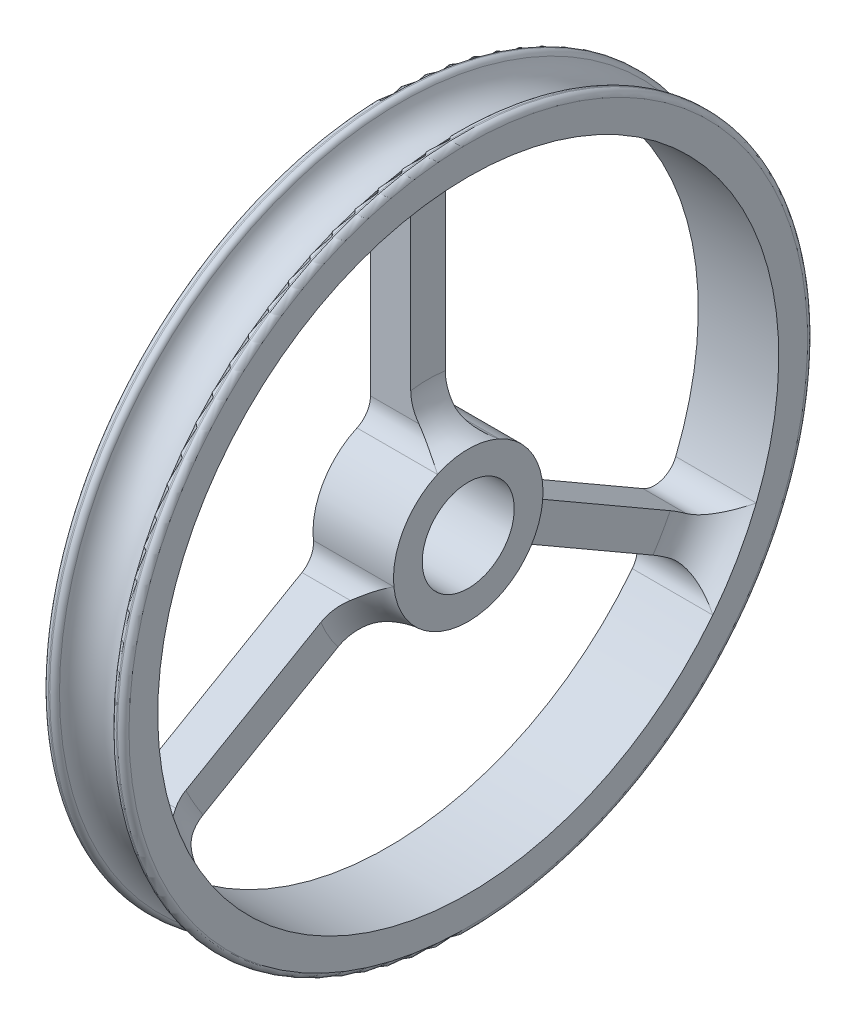
SolidWorks part; units mm, degrees
ref_plane "Front Plane" through (0, 0, 0) normal (0, 0, 1) x (1, 0, 0)
ref_plane "Top Plane" through (0, 0, 0) normal (0, 1, 0) x (1, 0, 0)
ref_plane "Right Plane" through (0, 0, 0) normal (1, 0, 0) x (0, 0, -1)
sketch "Sketch1" plane through (0, 0, 0) normal (0, 1, 0) x (1, 0, 0)
  line L0 (0, 4) -> (7, 4)
  line L1 (0, 0) -> (7, 0) construction
  line L2 (0, 4) -> (0, 6.5)
  line L3 (0, 30) -> (1.0181, 30)
  line L4 (7, 4) -> (7, 6.5)
  line L5 (0, 27) -> (7, 27)
  line L6 (0, 6.5) -> (7, 6.5)
  line L7 (5.9819, 30) -> (7, 30)
  line L8 (7, 27) -> (7, 30)
  line L9 (0, 27) -> (0, 30)
  arc A0 (1.0181, 30) -> (5.9819, 30) centre (3.5, 30.3) ccw
  dimension "D5" = 5
  dimension "D1" = 30
  dimension "D2" = 7
  dimension "D3" = 4
  dimension "D4" = 3
  dimension "D6" = 0.3
  dimension "D7" = 2.5
revolve "Revolve1" add sketch "Sketch1" angle 360 about L1
sketch "Sketch2" plane through (0, 0, 0) normal (-1, 0, 0) x (0, 0, 1)
  line L0 (0, 0) -> (0, 27)
  line L1 (0, 0) -> (-23.3827, -13.5)
  line L2 (0, 0) -> (23.3827, -13.5)
  line L3 (-24.0966, -12.1801) -> (0, 1.7321)
  line L4 (-1.5, -0.866) -> (-1.5, 26.9583)
  line L5 (1.5, -0.866) -> (1.5, 26.9583)
  line L6 (1.5, -0.866) -> (-22.5966, -14.7782)
  line L7 (0, 1.7321) -> (24.0966, -12.1801)
  line L8 (-1.5, -0.866) -> (22.5966, -14.7782)
  circle A0 centre (0, 0) radius 27 construction
  circle A1 centre (0, 0) radius 27
  circle M5 centre (0, 0) radius 6.5
  dimension "D1" = 120
  dimension "D2" = 120
  dimension "D3" = 1.5
  dimension "D4" = 1.5
  dimension "D5" = 1.5
extrude "Boss-Extrude1" add sketch "Sketch2" against normal blind 3.5 contours L8 A1 L2 M5 | L2 A1 L7 M5 | L1 A1 L6 M5 | L3 A1 L1 M5 | L0 A1 L4 M5 | L5 A1 L0 M5 region at (0, 16.7139, -0.7508) region at (0, 16.7139, 0.7508) region at (0, -9.0072, -14.0993) region at (0, -7.7067, -14.8501) region at (0, -7.7067, 14.8501) region at (0, -9.0072, 14.0993)
fillet "Fillet1" radius 2 12 edges at (1.75, -14.7782, -22.5966) (1.75, -4.4613, 4.7272) (1.75, -1.8632, -6.2272) (1.75, 6.3246, -1.5) (1.75, 6.3246, 1.5) (1.75, -1.8632, 6.2272) (1.75, -12.1801, -24.0966) (1.75, -12.1801, 24.0966) (1.75, -14.7782, 22.5966) (1.75, -4.4613, -4.7272) (1.75, 26.9583, -1.5) (1.75, 26.9583, 1.5)
fillet "Fillet2" radius 3.5 3 edges at (3.5, 6.5, 0) (3.5, -3.25, -5.6292) (3.5, -3.25, 5.6292)
fillet "Fillet3" radius 0.5 2 edges at (1.0181, 0, 30) (5.9819, 0, 30)
fillet "Fillet4" radius 0.5 2 edges at (0, 0, 30) (7, 0, 30)
fillet "Fillet5" radius 3.5 3 edges at (3.5, 27, 0) (3.5, -13.5, -23.3827) (3.5, -13.5, 23.3827)
